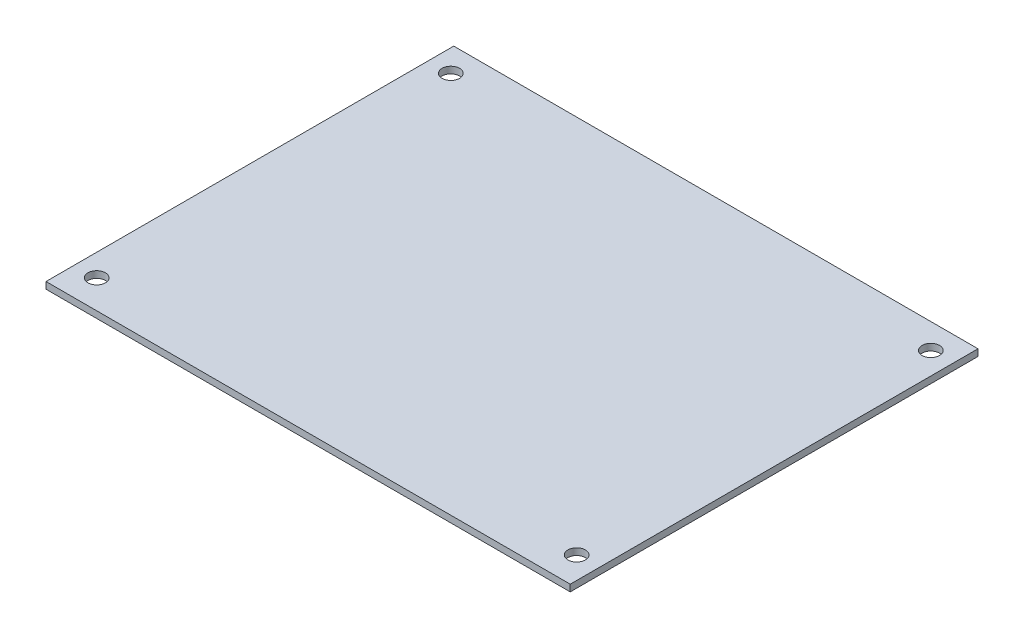
SolidWorks part; units mm, degrees
ref_plane "前基準面" through (0, 0, 0) normal (0, 0, 1) x (1, 0, 0)
ref_plane "上基準面" through (0, 0, 0) normal (0, 1, 0) x (1, 0, 0)
ref_plane "右基準面" through (0, 0, 0) normal (1, 0, 0) x (0, 0, -1)
sketch "草圖1" plane through (0, 0, 0) normal (0, 1, 0) x (1, 0, 0)
  line L1 (-45, 35) -> (45, 35)
  line L2 (-45, 35) -> (-45, -35)
  line L3 (-45, -35) -> (45, -35)
  line L4 (45, 35) -> (45, -35)
  line L5 (-45, 35) -> (45, -35) construction
  line L6 (-45, -35) -> (45, 35) construction
  point P0 (0, 0)
  dimension "D1" = 90
  dimension "D2" = 70
extrude "填料-伸長1" add sketch "草圖1" along normal blind 1.15
sketch "草圖2" plane through (0, 1.15, 0) normal (0, 1, 0) x (1, 0, 0)
  line L0 (45, 35) -> (-45, 35) construction
  line L1 (45, -35) -> (45, 35) construction
  line L2 (0, 35) -> (0, -35) construction
  line L3 (-45, -35) -> (45, -35) construction
  circle A0 centre (41.2, 30.7) radius 1.5
  circle A1 centre (41.2, -30.1) radius 1.5
  circle A2 centre (-41.2, -30.1) radius 1.5
  circle A3 centre (-41.2, 30.7) radius 1.5
  point P12 (0, 0)
  point P13 (41.2, -28.5623)
  dimension "D3" = 3
  dimension "D1" = 4.3
  dimension "D2" = 3.8
  dimension "D4" = 4.9
extrude "除料-伸長1" cut sketch "草圖2" against normal through all
sketch "草圖3" plane through (0, 1.15, 0) normal (0, 1, 0) x (1, 0, 0)
  text T0 "UP"
